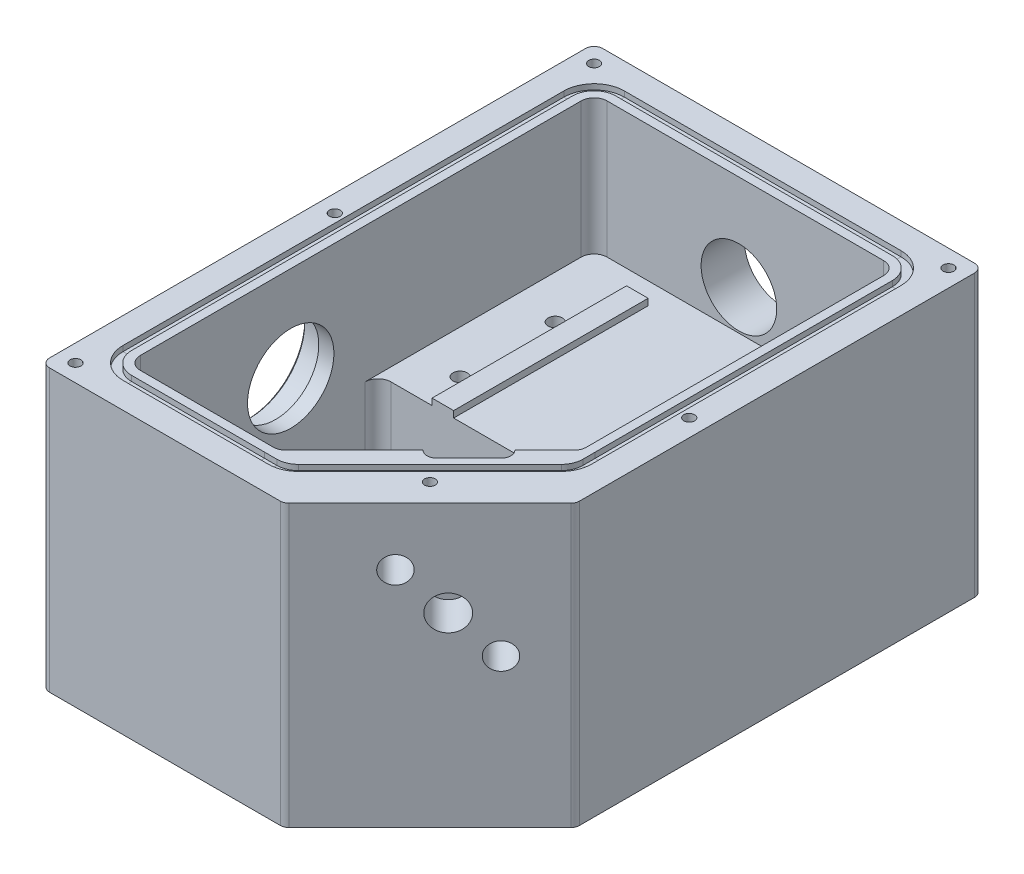
SolidWorks part; units mm, degrees
ref_plane "Front Plane" through (0, 0, 0) normal (0, 0, 1) x (1, 0, 0)
ref_plane "Top Plane" through (0, 0, 0) normal (0, 1, 0) x (1, 0, 0)
ref_plane "Right Plane" through (0, 0, 0) normal (1, 0, 0) x (0, 0, -1)
sketch "Sketch1" plane through (0, 0, 0) normal (0, 1, 0) x (1, 0, 0)
  line L1 (-45, -59) -> (45, -59)
  line L2 (-45, -59) -> (-45, 59)
  line L3 (-45, 59) -> (45, 59)
  line L4 (45, -59) -> (45, 59)
  line L5 (-45, -59) -> (45, 59) construction
  line L6 (-45, 59) -> (45, -59) construction
  point P0 (0, 0)
  dimension "D1" = 118
  dimension "D2" = 90
extrude "Boss-Extrude1" add sketch "Sketch1" along normal blind 15
sketch "Sketch3" plane through (0, 15, 0) normal (0, 1, 0) x (1, 0, 0)
  line L0 (45, -59) -> (45, 59) construction
  line L1 (-45, 59) -> (45, 59)
  line L2 (-45, 59) -> (-45, 9)
  line L3 (-45, 9) -> (45, 9)
  line L4 (45, 59) -> (45, 9)
  dimension "D1" = 50
extrude "Boss-Extrude3" add sketch "Sketch3" along normal blind 18.7
sketch "Sketch45" plane through (0, 0, -9) normal (0, 0, 1) x (1, 0, 0)
  line L1 (-22.5, 35.2) -> (-17.5, 35.2)
  line L2 (-22.5, 35.2) -> (-22.5, 33.7)
  line L3 (-22.5, 33.7) -> (-17.5, 33.7)
  line L4 (-17.5, 35.2) -> (-17.5, 33.7)
extrude "Boss-Extrude10" add sketch "Sketch45" against normal blind 45
sketch "Sketch6" plane through (0, 33.7, 0) normal (0, 1, 0) x (1, 0, 0)
  line L1 (-25, 18) -> (25, 18) construction
  line L2 (-25, 18) -> (-25, 40) construction
  line L3 (-25, 40) -> (25, 40) construction
  line L4 (25, 18) -> (25, 40) construction
  line L5 (-25, 18) -> (25, 40) construction
  line L6 (-25, 40) -> (25, 18) construction
  line L7 (-45, 9) -> (-22.5, 9) construction
  line L8 (-25, 22.18) -> (-25, 35.82) construction
  point P0 (0, 29)
  dimension "D1" = 22
  dimension "D3" = 20
hole_wizard "M4 Tapped Hole1" positions "3DSketch3" profile "Sketch7" tap size "M4" standard "ISO"
sketch3d "3DSketch3"
  point P0 (-25, 33.7, -40)
  point P3 (25, 33.7, -40)
  point P6 (25, 33.7, -18)
  point P9 (-25, 33.7, -18)
sketch "Sketch7" plane through (-25, 33.7, -40) normal (1, 0, 0) x (0, 0, 1)
  line L0 (0, 0) -> (0, 7.5954)
  line L1 (0, 7.5954) -> (1.65, 6.604)
  line L2 (1.65, 6.604) -> (1.65, 0)
  line L5 (1.65, 0) -> (0, 0)
  line L10 (0, 7.5954) -> (-1.65, 6.604) construction
  line L11 (0, -6.35) -> (0, 107.95) construction
  dimension "Tap Drill Dia." = 3.3
  dimension "Tap Drill Depth" = 6.604
  dimension "Drill Angle" = 118
cosmetic thread "Hole Thread1" parameters "D1"=3.048, "D2"=4
cosmetic thread "Hole Thread2" parameters "D1"=3.048, "D2"=4
cosmetic thread "Hole Thread3" parameters "D1"=3.048, "D2"=4
cosmetic thread "Hole Thread4" parameters "D1"=3.048, "D2"=4
sketch "Sketch9" plane through (0, 15, 0) normal (0, 1, 0) x (1, 0, 0)
  line L0 (45, -4) -> (-10, -59)
  line L1 (45, -59) -> (45, 9) construction
  line L2 (-45, -59) -> (45, -59) construction
  line L3 (-10, -59) -> (45, -59)
  line L4 (45, -59) -> (45, -4)
  dimension "D1" = 45
  dimension "D2" = 55
extrude "Boss-Extrude5" add sketch "Sketch9" along normal blind 50
sketch "Sketch10" plane through (0, 65, 0) normal (0, 1, 0) x (1, 0, 0)
  line L0 (45, -25.2132) -> (11.2132, -59)
  line L1 (45, -59) -> (45, -4) construction
  line L2 (-10, -59) -> (45, -59) construction
  line L3 (45, -4) -> (-10, -59) construction
  line L4 (11.2132, -59) -> (45, -59)
  line L5 (45, -59) -> (45, -25.2132)
  dimension "D1" = 15
extrude "Cut-Extrude2" cut sketch "Sketch10" against normal through all
ref_plane "Plane8" through (-7, 0, 7) normal (-0.7071, 0, 0.7071) x (0.7071, 0, 0.7071)
sketch "Sketch19" plane through (45, 0, 0) normal (1, 0, 0) x (0, 0, -1)
  line L1 (-25.2132, 65) -> (59, 65)
  line L2 (-25.2132, 65) -> (-25.2132, 0)
  line L3 (-25.2132, 0) -> (59, 0)
  line L4 (59, 65) -> (59, 0)
extrude "Boss-Extrude6" add sketch "Sketch19" against normal blind 10
sketch "Sketch20" plane through (0, 0, 59) normal (0, 0, 1) x (1, 0, 0)
  line L1 (11.2132, 65) -> (-45, 65)
  line L2 (11.2132, 65) -> (11.2132, 0)
  line L3 (11.2132, 0) -> (-45, 0)
  line L4 (-45, 65) -> (-45, 0)
extrude "Boss-Extrude7" add sketch "Sketch20" against normal blind 10
sketch "Sketch21" plane through (-45, 0, 0) normal (-1, 0, 0) x (0, 0, 1)
  line L1 (-59, 0) -> (59, 0)
  line L2 (-59, 0) -> (-59, 65)
  line L3 (-59, 65) -> (59, 65)
  line L4 (59, 0) -> (59, 65)
extrude "Boss-Extrude8" add sketch "Sketch21" against normal blind 10
sketch "Sketch22" plane through (0, 0, -59) normal (0, 0, -1) x (-1, 0, 0)
  line L1 (-45, 0) -> (45, 0)
  line L2 (-45, 0) -> (-45, 65)
  line L3 (-45, 65) -> (45, 65)
  line L4 (45, 0) -> (45, 65)
extrude "Boss-Extrude9" add sketch "Sketch22" along normal blind 10
fillet "Fillet1" radius 3 5 edges at (0, 40, 49) (35, 40, 14) (-35, 40, 49)
fillet "Fillet3" radius 3 2 edges at (35, 24.35, -9) (-35, 24.35, -9)
fillet "Fillet5" radius 2 5 edges at (-45, 32.5, 59) (11.2132, 32.5, 59) (-45, 32.5, -69) (45, 32.5, -69) (45, 32.5, 25.2132)
hole_wizard "CBORE for M5 Hex Head Bolt1" positions "3DSketch11" profile "Sketch49" counterbore size "M5" standard "ISO" end condition up to next
sketch3d "3DSketch11"
  line L0 (1.85, 43, 11.1991) -> (-68.0499, 43, 11.1991) construction
  point P0 (-45, 43, 11.1991)
sketch "Sketch49" plane through (-45, 43, 11.1991) normal (0, 1, 0) x (0, 0, 1)
  line L0 (0, 0) -> (0, 10)
  line L1 (0, 10) -> (10, 10)
  line L3 (10, 10) -> (10, 6.5)
  line L4 (10, 6.5) -> (12.75, 6.5)
  line L5 (12.75, 6.5) -> (12.75, 0)
  line L7 (12.75, 0) -> (0, 0)
  line L11 (0, -6.35) -> (0, 107.95) construction
  dimension "Thru Hole Dia." = 20
  dimension "Thru Hole Depth" = 10
  dimension "C'Bore Dia." = 25.5
  dimension "C'Bore Depth" = 6.5
chamfer "Chamfer1" distance 0.5 angle 45 1 edges at (-45, 43, 23.9491)
sketch "Sketch52" plane through (0, 65, 0) normal (0, 1, 0) x (1, 0, 0)
  line L16 (3, -50.2426) -> (36.2426, -17)
  line L17 (-32, -52) -> (-1.2426, -52)
  line L18 (-38, 56) -> (-38, -46)
  line L19 (32, 62) -> (-32, 62)
  line L20 (38, -12.7574) -> (38, 56)
  line L21 (3, -50.2426) -> (36.2426, -17)
  line L22 (-32, -52) -> (-1.2426, -52)
  line L23 (-38, 56) -> (-38, -46)
  line L24 (32, 62) -> (-32, 62)
  line L25 (38, -12.7574) -> (38, 56)
  arc A15 (-1.2426, -52) -> (3, -50.2426) centre (-1.2426, -46) ccw
  arc A16 (-38, -46) -> (-32, -52) centre (-32, -46) ccw
  arc A17 (-32, 62) -> (-38, 56) centre (-32, 56) ccw
  arc A18 (38, 56) -> (32, 62) centre (32, 56) ccw
  arc A19 (36.2426, -17) -> (38, -12.7574) centre (32, -12.7574) ccw
  arc A20 (-1.2426, -52) -> (3, -50.2426) centre (-1.2426, -46) ccw
  arc A21 (-38, -46) -> (-32, -52) centre (-32, -46) ccw
  arc A22 (-32, 62) -> (-38, 56) centre (-32, 56) ccw
  arc A23 (38, 56) -> (32, 62) centre (32, 56) ccw
  arc A24 (36.2426, -17) -> (38, -12.7574) centre (32, -12.7574) ccw
  dimension "D1" = 3
sketch "Sketch65" plane through (0, 65, 0) normal (0, 1, 0) x (1, 0, 0)
  line L5 (38, -12.7574) -> (38, -15.5858)
  line L6 (36.2426, -19.8284) -> (5.8284, -50.2426)
  line L7 (1.5858, -52) -> (-1.2426, -52)
  line L10 (3, -50.2426) -> (36.2426, -17)
  line L11 (-32, -52) -> (-1.2426, -52)
  line L12 (-38, 56) -> (-38, -46)
  line L13 (32, 62) -> (-32, 62)
  line L14 (38, -12.7574) -> (38, 56)
  line L15 (3, -50.2426) -> (36.2426, -17) construction
  line L16 (-32, -52) -> (-1.2426, -52)
  line L17 (-38, 56) -> (-38, -46)
  line L18 (32, 62) -> (-32, 62)
  line L19 (38, -12.7574) -> (38, 56)
  arc A5 (38, -15.5858) -> (36.2426, -19.8284) centre (32, -15.5858) cw
  arc A6 (5.8284, -50.2426) -> (1.5858, -52) centre (1.5858, -46) cw
  arc A10 (-1.2426, -52) -> (3, -50.2426) centre (-1.2426, -46) ccw
  arc A11 (-38, -46) -> (-32, -52) centre (-32, -46) ccw
  arc A12 (-32, 62) -> (-38, 56) centre (-32, 56) ccw
  arc A13 (38, 56) -> (32, 62) centre (32, 56) ccw
  arc A14 (36.2426, -17) -> (38, -12.7574) centre (32, -12.7574) ccw
  arc A15 (-1.2426, -52) -> (3, -50.2426) centre (-1.2426, -46) ccw construction
  arc A16 (-38, -46) -> (-32, -52) centre (-32, -46) ccw
  arc A17 (-32, 62) -> (-38, 56) centre (-32, 56) ccw
  arc A18 (38, 56) -> (32, 62) centre (32, 56) ccw
  arc A19 (36.2426, -17) -> (38, -12.7574) centre (32, -12.7574) ccw construction
  dimension "D2" = 6
  dimension "D3" = 2
  dimension "D1" = 3
ref_plane "Plane32" through (0, 0, -56) normal (0, 0, -1) x (-1, 0, 0)
sketch "Sketch66" plane through (0, 0, -56) normal (0, 0, -1) x (-1, 0, 0)
  line L1 (-39, 66.25) -> (-37, 66.25)
  line L2 (-39, 66.25) -> (-39, 63.75)
  line L3 (-39, 63.75) -> (-37, 63.75)
  line L4 (-37, 66.25) -> (-37, 63.75)
  line L5 (-39, 66.25) -> (-37, 63.75) construction
  line L6 (-39, 63.75) -> (-37, 66.25) construction
  point P0 (-38, 65)
  dimension "D1" = 2.5
  dimension "D2" = 2
sweep "Cut-Sweep2" cut profiles "Sketch66" path "Sketch65"
mirror "Mirror2" about plane through (0, 0, 0) normal (1, 0, 0) of "Boss-Extrude10"
hole_wizard "M20 Tapped Hole1" positions "3DSketch9" profile "Sketch46" tap size "M20" standard "ISO" end condition up to next
sketch3d "3DSketch9"
  line L0 (-1.5, 42.9, -29.8) -> (-1.5, 42.9, -80.5766) construction
  point P0 (-1.5, 42.9, -69)
sketch "Sketch46" plane through (-1.5, 42.9, -69) normal (1, 0, 0) x (0, 1, 0)
  line L0 (0, 0) -> (0, 10)
  line L1 (0, 10) -> (8.75, 10)
  line L2 (8.75, 10) -> (8.75, 0)
  line L5 (8.75, 0) -> (0, 0)
  line L11 (0, -6.35) -> (0, 107.95) construction
  dimension "Thru Tap Drill Dia." = 17.5
  dimension "Thru Tap Drill Depth" = 10
cosmetic thread "Hole Thread19" parameters "D2"=20
sketch "Sketch47" plane through (0, 65, 0) normal (0, 1, 0) x (1, 0, 0)
  line L0 (-45, 5) -> (45, 5) construction
  line L1 (-45, 67) -> (-45, -57) construction
  line L2 (45, -24.3848) -> (45, 67) construction
  line L3 (0, 69) -> (0, -59) construction
  line L4 (-43, 69) -> (43, 69) construction
  line L5 (-43, -59) -> (10.3848, -59) construction
  line L6 (28.1066, -42.1066) -> (17.5, -31.5) construction
  line L7 (44.4142, -25.799) -> (11.799, -58.4142) construction
  line L8 (34.1213, -14.8787) -> (0.8787, -48.1213) construction
  point P0 (-41, 65)
  point P1 (41, 65)
  point P2 (41, 5)
  point P3 (-41, 5)
  point P4 (-41, -55)
  point P6 (23.864, -37.864)
  dimension "D1" = 4
  dimension "D2" = 4
  dimension "D3" = 4
  dimension "D4" = 6
  dimension "D5" = 4
hole_wizard "M3 Tapped Hole1" positions "3DSketch10" profile "Sketch48" tap size "M3" standard "ISO"
sketch3d "3DSketch10"
  point P0 (-41, 65, -65)
  point P3 (41, 65, -65)
  point P6 (41, 65, -5)
  point P9 (-41, 65, -5)
  point P12 (-41, 65, 55)
  point P18 (23.864, 65, 37.864)
sketch "Sketch48" plane through (-41, 65, -65) normal (1, 0, 0) x (0, 0, 1)
  line L0 (0, 0) -> (0, 9.2511)
  line L1 (0, 9.2511) -> (1.25, 8.5)
  line L2 (1.25, 8.5) -> (1.25, 0)
  line L5 (1.25, 0) -> (0, 0)
  line L10 (0, 9.2511) -> (-1.25, 8.5) construction
  line L11 (0, -6.35) -> (0, 107.95) construction
  dimension "Tap Drill Dia." = 2.5
  dimension "Tap Drill Depth" = 8.5
  dimension "Drill Angle" = 118
cosmetic thread "Hole Thread21" parameters "D1"=6, "D2"=3
cosmetic thread "Hole Thread23" parameters "D1"=6, "D2"=3
cosmetic thread "Hole Thread24" parameters "D1"=6, "D2"=3
cosmetic thread "Hole Thread25" parameters "D1"=6, "D2"=3
cosmetic thread "Hole Thread26" parameters "D1"=6, "D2"=3
cosmetic thread "Hole Thread27" parameters "D1"=6, "D2"=3
hole_wizard "Ø3.0 (3) Diameter Hole1" positions "3DSketch12" profile "Sketch56" hole size "Ø3.0" standard "ISO"
sketch3d "3DSketch12"
  line L0 (-23.15, 10, -7.5) -> (-23.15, 50, -7.5) construction
  line L1 (26.85, 50, -7.5) -> (26.85, 10, -7.5) construction
  point P0 (-23.15, 15, -7.5)
  point P2 (26.85, 15, -7.5)
sketch "Sketch56" plane through (-23.15, 15, -7.5) normal (1, 0, 0) x (0, 0, 1)
  line L0 (0, 0) -> (0, 5.9003)
  line L1 (0, 5.9003) -> (1.5, 4.999)
  line L2 (1.5, 4.999) -> (1.5, 0)
  line L5 (1.5, 0) -> (0, 0)
  line L10 (0, 5.9003) -> (-1.5, 4.999) construction
  line L11 (0, -6.35) -> (0, 107.95) construction
  dimension "Hole Dia." = 3
  dimension "Hole Depth" = 4.999
  dimension "Drill Angle" = 118
sketch "Sketch55" plane through (0, 15, 0) normal (0, 1, 0) x (1, 0, 0)
  line L4 (26.85, 7.5) -> (-23.15, 7.5)
  line L5 (26.85, -7.5) -> (26.85, 7.5)
  line L6 (-18.15, -12.5) -> (21.85, -12.5)
  line L7 (-23.15, 7.5) -> (-23.15, -7.5)
  line L8 (26.85, 7.5) -> (-23.15, 7.5)
  line L9 (26.85, -7.5) -> (26.85, 7.5)
  line L10 (-18.15, -12.5) -> (21.85, -12.5)
  line L11 (-23.15, 7.5) -> (-23.15, -7.5)
  arc A2 (21.85, -12.5) -> (26.85, -7.5) centre (21.85, -7.5) ccw
  arc A3 (-23.15, -7.5) -> (-18.15, -12.5) centre (-18.15, -7.5) ccw
  arc A4 (21.85, -12.5) -> (26.85, -7.5) centre (21.85, -7.5) ccw
  arc A5 (-23.15, -7.5) -> (-18.15, -12.5) centre (-18.15, -7.5) ccw
  dimension "D1" = 0
extrude "Cut-Extrude8" cut sketch "Sketch55" against normal up to surface (5 mm away)
ref_plane "Plane30" through (-4.8787, 0, 4.8787) normal (-0.7071, 0, 0.7071) x (0.7071, 0, 0.7071)
sketch "Sketch57" plane through (35.1066, 0, 35.1066) normal (0.7071, 0, 0.7071) x (0.7071, 0, -0.7071)
  circle A0 centre (-15.5355, 51.636) radius 3.067 construction
  circle A1 centre (1.7365, 34.364) radius 3.0671 construction
  circle A2 centre (-15.5355, 51.636) radius 3.067
  circle A3 centre (1.7365, 34.364) radius 3.067
extrude "KMSS_brass_pin_locator" cut sketch "Sketch57" against normal up to next
hole_wizard "CBORE for M4 Hex Socket Head Cap Screw1" positions "3DSketch13" profile "Sketch59" counterbore size "M4" standard "ISO" end condition up to next
sketch3d "3DSketch13"
  point P0 (30.2279, 43, 39.9853)
sketch "Sketch59" plane through (30.2279, 43, 39.9853) normal (0, 1, 0) x (0.7071, 0, -0.7071)
  line L0 (0, 0) -> (0, 15)
  line L1 (0, 15) -> (2.15, 15)
  line L3 (2.15, 15) -> (2.15, 9.4)
  line L4 (2.15, 9.4) -> (4, 9.4)
  line L5 (4, 9.4) -> (4, 0)
  line L7 (4, 0) -> (0, 0)
  line L11 (0, -6.35) -> (0, 107.95) construction
  dimension "Thru Hole Dia." = 4.3
  dimension "Thru Hole Depth" = 15
  dimension "C'Bore Dia." = 8
  dimension "C'Bore Depth" = 9.4
hole_wizard "Ø4.5 (4.5) Diameter Hole2" positions "3DSketch14" profile "Sketch60" hole size "Ø4.5" standard "ISO"
sketch3d "3DSketch14"
  line L1 (34.1213, 65, 14.8787) -> (0.8787, 65, 48.1213) construction
  point P0 (25.7338, 65, 23.2662)
sketch "Sketch60" plane through (25.7338, 65, 23.2662) normal (1, 0, 0) x (0, 0, 1)
  line L0 (0, 0) -> (0, 27.1509)
  line L1 (0, 27.1509) -> (2.25, 25.799)
  line L2 (2.25, 25.799) -> (2.25, 0)
  line L5 (2.25, 0) -> (0, 0)
  line L10 (0, 27.1509) -> (-2.25, 25.799) construction
  line L11 (0, -6.35) -> (0, 107.95) construction
  dimension "Hole Dia." = 4.5
  dimension "Hole Depth" = 25.799
  dimension "Drill Angle" = 118
hole_wizard "Ø4.5 (4.5) Diameter Slot1" positions "Sketch69" profile "Sketch67" size "Ø4.5" standard "ISO" slot yes
sketch "Sketch69" plane through (0, 65, 0) normal (0, 1, 0) x (1, 0, 0)
  line L3 (16.7182, -32.2818) -> (27.3248, -21.6752) construction
  line L4 (34.1213, -14.8787) -> (27.3248, -21.6752) construction
  point P0 (22.0215, -26.9785)
  dimension "D1" = 15
sketch "Sketch67" plane through (22.0215, 65, 26.9785) normal (1, 0, 0) x (0, 0, 1)
  line L0 (0, 0) -> (0, 17.3509)
  line L1 (0, 17.3509) -> (2.25, 15.999)
  line L2 (2.25, 15.999) -> (2.25, 0)
  line L5 (2.25, 0) -> (0, 0)
  line L10 (0, 17.3509) -> (-2.25, 15.999) construction
  line L11 (0, -6.35) -> (0, 107.95) construction
  dimension "Hole Dia." = 4.5
  dimension "Hole Depth" = 15.999
  dimension "Drill Angle" = 118
